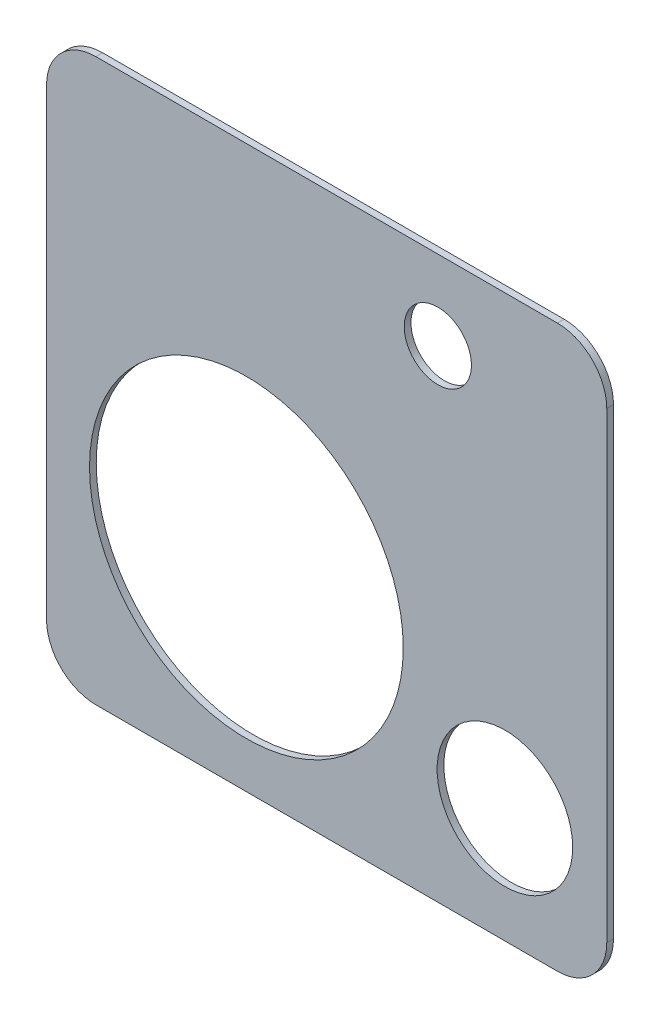
SolidWorks part; units mm, degrees
material "Pine"
ref_plane "Front Plane" through (0, 0, 0) normal (0, 0, 1) x (1, 0, 0)
ref_plane "Top Plane" through (0, 0, 0) normal (0, 1, 0) x (1, 0, 0)
ref_plane "Right Plane" through (0, 0, 0) normal (1, 0, 0) x (0, 0, -1)
sketch "Sketch1" plane through (0, 0, 0) normal (0, 0, 1) x (1, 0, 0)
  line L1 (0, 0) -> (500, 0)
  line L2 (0, 0) -> (0, 501)
  line L3 (0, 501) -> (500, 501)
  line L4 (500, 0) -> (500, 501)
  dimension "D1" = 500
  dimension "D2" = 501
extrude "Boss-Extrude1" add sketch "Sketch1" along normal blind 6
fillet "Fillet1" radius 44 4 edges at (0, 0, 3) (500, 0, 3) (0, 501, 3) (500, 501, 3)
sketch "Sketch2" plane through (0, 0, 6) normal (0, 0, 1) x (1, 0, 0)
  circle A0 centre (178.369, 181.0347) radius 156
  dimension "D1" = 312
sketch "Sketch3" plane through (0, 0, 6) normal (0, 0, 1) x (1, 0, 0)
  circle A1 centre (178.369, 181.0347) radius 140
  dimension "D1" = 280
extrude "Cut-Extrude2" cut sketch "Sketch3" against normal through all
sketch "Sketch4" plane through (0, 0, 6) normal (0, 0, 1) x (1, 0, 0)
  circle A0 centre (409.1034, 102.5162) radius 72.5
  dimension "D1" = 145
sketch "Sketch5" plane through (0, 0, 6) normal (0, 0, 1) x (1, 0, 0)
  circle A0 centre (409.1034, 102.5162) radius 60.5
  dimension "D1" = 121
extrude "Cut-Extrude3" cut sketch "Sketch5" against normal through all
sketch "Sketch6" plane through (0, 0, 6) normal (0, 0, 1) x (1, 0, 0)
  line L0 (500, 360) -> (0, 360)
  line L1 (500, 44) -> (500, 457) construction
  line L2 (0, 457) -> (0, 44) construction
  line L3 (44, 0) -> (456, 0) construction
  line L4 (456, 501) -> (44, 501) construction
  circle A0 centre (349.2286, 430) radius 50
  circle A1 centre (349.2286, 430) radius 30
  dimension "D1" = 100
  dimension "D3" = 60
  dimension "D2" = 360
  dimension "D4" = 71
extrude "Cut-Extrude5" cut sketch "Sketch6" against normal through all contours A1 region at (349.2286, 430, 6)
sketch "Sketch7" plane through (0, 0, 6) normal (0, 0, 1) x (1, 0, 0)
  line L0 (0, 457) -> (0, 44) construction
  line L1 (456, 501) -> (44, 501) construction
  text T0 "ouisician" font "Century Gothic" height in points 72
  dimension "D1" = 80
  dimension "D2" = 80
sketch "Sketch10" plane through (0, 0, 6) normal (0, 0, 1) x (1, 0, 0)
  line L0 (0, 366) -> (500, 366)
  line L1 (0, 457) -> (0, 44) construction
  line L2 (500, 44) -> (500, 457) construction
  line L3 (456, 501) -> (44, 501) construction
  line L4 (0, 360) -> (500, 360)
  line L5 (44, 0) -> (456, 0) construction
  dimension "D1" = 500
  dimension "D2" = 135
  dimension "D3" = 360
